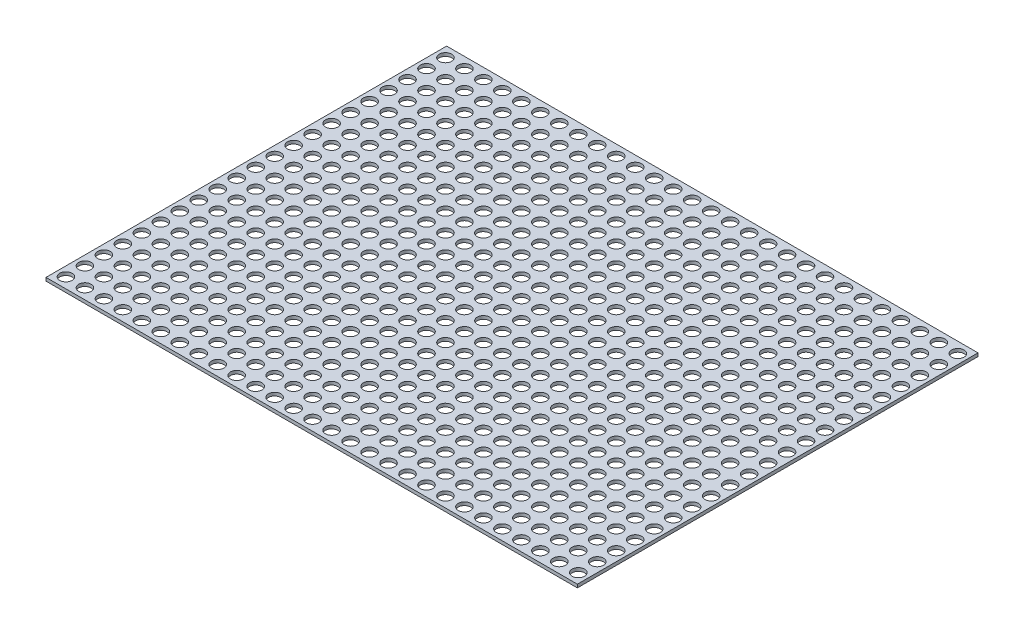
SolidWorks part; units mm, degrees
ref_plane "Front Plane" through (0, 0, 0) normal (0, 0, 1) x (1, 0, 0)
ref_plane "Top Plane" through (0, 0, 0) normal (0, 1, 0) x (1, 0, 0)
ref_plane "Right Plane" through (0, 0, 0) normal (1, 0, 0) x (0, 0, -1)
sketch "Sketch1" plane through (0, 0, 0) normal (0, 1, 0) x (1, 0, 0)
  line L0 (4.5, 4.95) -> (13.5, 4.95) construction
  line L1 (0, 0) -> (252, 0)
  line L2 (0, 0) -> (0, 190)
  line L3 (0, 190) -> (252, 190)
  line L4 (252, 0) -> (252, 190)
  line L5 (4.5, 4.95) -> (4.5, 13.95) construction
  circle A0 centre (4.5, 4.95) radius 2.95
  circle A1 centre (13.5, 4.95) radius 2.95
  circle A2 centre (22.5, 4.95) radius 2.95
  circle A3 centre (31.5, 4.95) radius 2.95
  circle A4 centre (40.5, 4.95) radius 2.95
  circle A5 centre (49.5, 4.95) radius 2.95
  circle A6 centre (58.5, 4.95) radius 2.95
  circle A7 centre (67.5, 4.95) radius 2.95
  circle A8 centre (76.5, 4.95) radius 2.95
  circle A9 centre (85.5, 4.95) radius 2.95
  circle A10 centre (94.5, 4.95) radius 2.95
  circle A11 centre (103.5, 4.95) radius 2.95
  circle A12 centre (112.5, 4.95) radius 2.95
  circle A13 centre (121.5, 4.95) radius 2.95
  circle A14 centre (130.5, 4.95) radius 2.95
  circle A15 centre (139.5, 4.95) radius 2.95
  circle A16 centre (148.5, 4.95) radius 2.95
  circle A17 centre (157.5, 4.95) radius 2.95
  circle A18 centre (166.5, 4.95) radius 2.95
  circle A19 centre (175.5, 4.95) radius 2.95
  circle A20 centre (184.5, 4.95) radius 2.95
  circle A21 centre (193.5, 4.95) radius 2.95
  circle A22 centre (202.5, 4.95) radius 2.95
  circle A23 centre (211.5, 4.95) radius 2.95
  circle A24 centre (220.5, 4.95) radius 2.95
  circle A25 centre (229.5, 4.95) radius 2.95
  circle A26 centre (238.5, 4.95) radius 2.95
  circle A27 centre (247.5, 4.95) radius 2.95
  circle A28 centre (13.5, 13.95) radius 2.95
  circle A29 centre (22.5, 13.95) radius 2.95
  circle A30 centre (31.5, 13.95) radius 2.95
  circle A31 centre (40.5, 13.95) radius 2.95
  circle A32 centre (49.5, 13.95) radius 2.95
  circle A33 centre (58.5, 13.95) radius 2.95
  circle A34 centre (67.5, 13.95) radius 2.95
  circle A35 centre (76.5, 13.95) radius 2.95
  circle A36 centre (85.5, 13.95) radius 2.95
  circle A37 centre (94.5, 13.95) radius 2.95
  circle A38 centre (103.5, 13.95) radius 2.95
  circle A39 centre (112.5, 13.95) radius 2.95
  circle A40 centre (121.5, 13.95) radius 2.95
  circle A41 centre (130.5, 13.95) radius 2.95
  circle A42 centre (139.5, 13.95) radius 2.95
  circle A43 centre (148.5, 13.95) radius 2.95
  circle A44 centre (157.5, 13.95) radius 2.95
  circle A45 centre (166.5, 13.95) radius 2.95
  circle A46 centre (175.5, 13.95) radius 2.95
  circle A47 centre (184.5, 13.95) radius 2.95
  circle A48 centre (193.5, 13.95) radius 2.95
  circle A49 centre (202.5, 13.95) radius 2.95
  circle A50 centre (211.5, 13.95) radius 2.95
  circle A51 centre (220.5, 13.95) radius 2.95
  circle A52 centre (229.5, 13.95) radius 2.95
  circle A53 centre (238.5, 13.95) radius 2.95
  circle A54 centre (247.5, 13.95) radius 2.95
  circle A55 centre (13.5, 22.95) radius 2.95
  circle A56 centre (22.5, 22.95) radius 2.95
  circle A57 centre (31.5, 22.95) radius 2.95
  circle A58 centre (40.5, 22.95) radius 2.95
  circle A59 centre (49.5, 22.95) radius 2.95
  circle A60 centre (58.5, 22.95) radius 2.95
  circle A61 centre (67.5, 22.95) radius 2.95
  circle A62 centre (76.5, 22.95) radius 2.95
  circle A63 centre (85.5, 22.95) radius 2.95
  circle A64 centre (94.5, 22.95) radius 2.95
  circle A65 centre (103.5, 22.95) radius 2.95
  circle A66 centre (112.5, 22.95) radius 2.95
  circle A67 centre (121.5, 22.95) radius 2.95
  circle A68 centre (130.5, 22.95) radius 2.95
  circle A69 centre (139.5, 22.95) radius 2.95
  circle A70 centre (148.5, 22.95) radius 2.95
  circle A71 centre (157.5, 22.95) radius 2.95
  circle A72 centre (166.5, 22.95) radius 2.95
  circle A73 centre (175.5, 22.95) radius 2.95
  circle A74 centre (184.5, 22.95) radius 2.95
  circle A75 centre (193.5, 22.95) radius 2.95
  circle A76 centre (202.5, 22.95) radius 2.95
  circle A77 centre (211.5, 22.95) radius 2.95
  circle A78 centre (220.5, 22.95) radius 2.95
  circle A79 centre (229.5, 22.95) radius 2.95
  circle A80 centre (238.5, 22.95) radius 2.95
  circle A81 centre (247.5, 22.95) radius 2.95
  circle A82 centre (13.5, 31.95) radius 2.95
  circle A83 centre (22.5, 31.95) radius 2.95
  circle A84 centre (31.5, 31.95) radius 2.95
  circle A85 centre (40.5, 31.95) radius 2.95
  circle A86 centre (49.5, 31.95) radius 2.95
  circle A87 centre (58.5, 31.95) radius 2.95
  circle A88 centre (67.5, 31.95) radius 2.95
  circle A89 centre (76.5, 31.95) radius 2.95
  circle A90 centre (85.5, 31.95) radius 2.95
  circle A91 centre (94.5, 31.95) radius 2.95
  circle A92 centre (103.5, 31.95) radius 2.95
  circle A93 centre (112.5, 31.95) radius 2.95
  circle A94 centre (121.5, 31.95) radius 2.95
  circle A95 centre (130.5, 31.95) radius 2.95
  circle A96 centre (139.5, 31.95) radius 2.95
  circle A97 centre (148.5, 31.95) radius 2.95
  circle A98 centre (157.5, 31.95) radius 2.95
  circle A99 centre (166.5, 31.95) radius 2.95
  circle A100 centre (175.5, 31.95) radius 2.95
  circle A101 centre (184.5, 31.95) radius 2.95
  circle A102 centre (193.5, 31.95) radius 2.95
  circle A103 centre (202.5, 31.95) radius 2.95
  circle A104 centre (211.5, 31.95) radius 2.95
  circle A105 centre (220.5, 31.95) radius 2.95
  circle A106 centre (229.5, 31.95) radius 2.95
  circle A107 centre (238.5, 31.95) radius 2.95
  circle A108 centre (247.5, 31.95) radius 2.95
  circle A109 centre (13.5, 40.95) radius 2.95
  circle A110 centre (22.5, 40.95) radius 2.95
  circle A111 centre (31.5, 40.95) radius 2.95
  circle A112 centre (40.5, 40.95) radius 2.95
  circle A113 centre (49.5, 40.95) radius 2.95
  circle A114 centre (58.5, 40.95) radius 2.95
  circle A115 centre (67.5, 40.95) radius 2.95
  circle A116 centre (76.5, 40.95) radius 2.95
  circle A117 centre (85.5, 40.95) radius 2.95
  circle A118 centre (94.5, 40.95) radius 2.95
  circle A119 centre (103.5, 40.95) radius 2.95
  circle A120 centre (112.5, 40.95) radius 2.95
  circle A121 centre (121.5, 40.95) radius 2.95
  circle A122 centre (130.5, 40.95) radius 2.95
  circle A123 centre (139.5, 40.95) radius 2.95
  circle A124 centre (148.5, 40.95) radius 2.95
  circle A125 centre (157.5, 40.95) radius 2.95
  circle A126 centre (166.5, 40.95) radius 2.95
  circle A127 centre (175.5, 40.95) radius 2.95
  circle A128 centre (184.5, 40.95) radius 2.95
  circle A129 centre (193.5, 40.95) radius 2.95
  circle A130 centre (202.5, 40.95) radius 2.95
  circle A131 centre (211.5, 40.95) radius 2.95
  circle A132 centre (220.5, 40.95) radius 2.95
  circle A133 centre (229.5, 40.95) radius 2.95
  circle A134 centre (238.5, 40.95) radius 2.95
  circle A135 centre (247.5, 40.95) radius 2.95
  circle A136 centre (13.5, 49.95) radius 2.95
  circle A137 centre (22.5, 49.95) radius 2.95
  circle A138 centre (31.5, 49.95) radius 2.95
  circle A139 centre (40.5, 49.95) radius 2.95
  circle A140 centre (49.5, 49.95) radius 2.95
  circle A141 centre (58.5, 49.95) radius 2.95
  circle A142 centre (67.5, 49.95) radius 2.95
  circle A143 centre (76.5, 49.95) radius 2.95
  circle A144 centre (85.5, 49.95) radius 2.95
  circle A145 centre (94.5, 49.95) radius 2.95
  circle A146 centre (103.5, 49.95) radius 2.95
  circle A147 centre (112.5, 49.95) radius 2.95
  circle A148 centre (121.5, 49.95) radius 2.95
  circle A149 centre (130.5, 49.95) radius 2.95
  circle A150 centre (139.5, 49.95) radius 2.95
  circle A151 centre (148.5, 49.95) radius 2.95
  circle A152 centre (157.5, 49.95) radius 2.95
  circle A153 centre (166.5, 49.95) radius 2.95
  circle A154 centre (175.5, 49.95) radius 2.95
  circle A155 centre (184.5, 49.95) radius 2.95
  circle A156 centre (193.5, 49.95) radius 2.95
  circle A157 centre (202.5, 49.95) radius 2.95
  circle A158 centre (211.5, 49.95) radius 2.95
  circle A159 centre (220.5, 49.95) radius 2.95
  circle A160 centre (229.5, 49.95) radius 2.95
  circle A161 centre (238.5, 49.95) radius 2.95
  circle A162 centre (247.5, 49.95) radius 2.95
  circle A163 centre (13.5, 58.95) radius 2.95
  circle A164 centre (22.5, 58.95) radius 2.95
  circle A165 centre (31.5, 58.95) radius 2.95
  circle A166 centre (40.5, 58.95) radius 2.95
  circle A167 centre (49.5, 58.95) radius 2.95
  circle A168 centre (58.5, 58.95) radius 2.95
  circle A169 centre (67.5, 58.95) radius 2.95
  circle A170 centre (76.5, 58.95) radius 2.95
  circle A171 centre (85.5, 58.95) radius 2.95
  circle A172 centre (94.5, 58.95) radius 2.95
  circle A173 centre (103.5, 58.95) radius 2.95
  circle A174 centre (112.5, 58.95) radius 2.95
  circle A175 centre (121.5, 58.95) radius 2.95
  circle A176 centre (130.5, 58.95) radius 2.95
  circle A177 centre (139.5, 58.95) radius 2.95
  circle A178 centre (148.5, 58.95) radius 2.95
  circle A179 centre (157.5, 58.95) radius 2.95
  circle A180 centre (166.5, 58.95) radius 2.95
  circle A181 centre (175.5, 58.95) radius 2.95
  circle A182 centre (184.5, 58.95) radius 2.95
  circle A183 centre (193.5, 58.95) radius 2.95
  circle A184 centre (202.5, 58.95) radius 2.95
  circle A185 centre (211.5, 58.95) radius 2.95
  circle A186 centre (220.5, 58.95) radius 2.95
  circle A187 centre (229.5, 58.95) radius 2.95
  circle A188 centre (238.5, 58.95) radius 2.95
  circle A189 centre (247.5, 58.95) radius 2.95
  circle A190 centre (13.5, 67.95) radius 2.95
  circle A191 centre (22.5, 67.95) radius 2.95
  circle A192 centre (31.5, 67.95) radius 2.95
  circle A193 centre (40.5, 67.95) radius 2.95
  circle A194 centre (49.5, 67.95) radius 2.95
  circle A195 centre (58.5, 67.95) radius 2.95
  circle A196 centre (67.5, 67.95) radius 2.95
  circle A197 centre (76.5, 67.95) radius 2.95
  circle A198 centre (85.5, 67.95) radius 2.95
  circle A199 centre (94.5, 67.95) radius 2.95
  circle A200 centre (103.5, 67.95) radius 2.95
  circle A201 centre (112.5, 67.95) radius 2.95
  circle A202 centre (121.5, 67.95) radius 2.95
  circle A203 centre (130.5, 67.95) radius 2.95
  circle A204 centre (139.5, 67.95) radius 2.95
  circle A205 centre (148.5, 67.95) radius 2.95
  circle A206 centre (157.5, 67.95) radius 2.95
  circle A207 centre (166.5, 67.95) radius 2.95
  circle A208 centre (175.5, 67.95) radius 2.95
  circle A209 centre (184.5, 67.95) radius 2.95
  circle A210 centre (193.5, 67.95) radius 2.95
  circle A211 centre (202.5, 67.95) radius 2.95
  circle A212 centre (211.5, 67.95) radius 2.95
  circle A213 centre (220.5, 67.95) radius 2.95
  circle A214 centre (229.5, 67.95) radius 2.95
  circle A215 centre (238.5, 67.95) radius 2.95
  circle A216 centre (247.5, 67.95) radius 2.95
  circle A217 centre (13.5, 76.95) radius 2.95
  circle A218 centre (22.5, 76.95) radius 2.95
  circle A219 centre (31.5, 76.95) radius 2.95
  circle A220 centre (40.5, 76.95) radius 2.95
  circle A221 centre (49.5, 76.95) radius 2.95
  circle A222 centre (58.5, 76.95) radius 2.95
  circle A223 centre (67.5, 76.95) radius 2.95
  circle A224 centre (76.5, 76.95) radius 2.95
  circle A225 centre (85.5, 76.95) radius 2.95
  circle A226 centre (94.5, 76.95) radius 2.95
  circle A227 centre (103.5, 76.95) radius 2.95
  circle A228 centre (112.5, 76.95) radius 2.95
  circle A229 centre (121.5, 76.95) radius 2.95
  circle A230 centre (130.5, 76.95) radius 2.95
  circle A231 centre (139.5, 76.95) radius 2.95
  circle A232 centre (148.5, 76.95) radius 2.95
  circle A233 centre (157.5, 76.95) radius 2.95
  circle A234 centre (166.5, 76.95) radius 2.95
  circle A235 centre (175.5, 76.95) radius 2.95
  circle A236 centre (184.5, 76.95) radius 2.95
  circle A237 centre (193.5, 76.95) radius 2.95
  circle A238 centre (202.5, 76.95) radius 2.95
  circle A239 centre (211.5, 76.95) radius 2.95
  circle A240 centre (220.5, 76.95) radius 2.95
  circle A241 centre (229.5, 76.95) radius 2.95
  circle A242 centre (238.5, 76.95) radius 2.95
  circle A243 centre (247.5, 76.95) radius 2.95
  circle A244 centre (13.5, 85.95) radius 2.95
  circle A245 centre (22.5, 85.95) radius 2.95
  circle A246 centre (31.5, 85.95) radius 2.95
  circle A247 centre (40.5, 85.95) radius 2.95
  circle A248 centre (49.5, 85.95) radius 2.95
  circle A249 centre (58.5, 85.95) radius 2.95
  circle A250 centre (67.5, 85.95) radius 2.95
  circle A251 centre (76.5, 85.95) radius 2.95
  circle A252 centre (85.5, 85.95) radius 2.95
  circle A253 centre (94.5, 85.95) radius 2.95
  circle A254 centre (103.5, 85.95) radius 2.95
  circle A255 centre (112.5, 85.95) radius 2.95
  circle A256 centre (121.5, 85.95) radius 2.95
  circle A257 centre (130.5, 85.95) radius 2.95
  circle A258 centre (139.5, 85.95) radius 2.95
  circle A259 centre (148.5, 85.95) radius 2.95
  circle A260 centre (157.5, 85.95) radius 2.95
  circle A261 centre (166.5, 85.95) radius 2.95
  circle A262 centre (175.5, 85.95) radius 2.95
  circle A263 centre (184.5, 85.95) radius 2.95
  circle A264 centre (193.5, 85.95) radius 2.95
  circle A265 centre (202.5, 85.95) radius 2.95
  circle A266 centre (211.5, 85.95) radius 2.95
  circle A267 centre (220.5, 85.95) radius 2.95
  circle A268 centre (229.5, 85.95) radius 2.95
  circle A269 centre (238.5, 85.95) radius 2.95
  circle A270 centre (247.5, 85.95) radius 2.95
  circle A271 centre (13.5, 94.95) radius 2.95
  circle A272 centre (22.5, 94.95) radius 2.95
  circle A273 centre (31.5, 94.95) radius 2.95
  circle A274 centre (40.5, 94.95) radius 2.95
  circle A275 centre (49.5, 94.95) radius 2.95
  circle A276 centre (58.5, 94.95) radius 2.95
  circle A277 centre (67.5, 94.95) radius 2.95
  circle A278 centre (76.5, 94.95) radius 2.95
  circle A279 centre (85.5, 94.95) radius 2.95
  circle A280 centre (94.5, 94.95) radius 2.95
  circle A281 centre (103.5, 94.95) radius 2.95
  circle A282 centre (112.5, 94.95) radius 2.95
  circle A283 centre (121.5, 94.95) radius 2.95
  circle A284 centre (130.5, 94.95) radius 2.95
  circle A285 centre (139.5, 94.95) radius 2.95
  circle A286 centre (148.5, 94.95) radius 2.95
  circle A287 centre (157.5, 94.95) radius 2.95
  circle A288 centre (166.5, 94.95) radius 2.95
  circle A289 centre (175.5, 94.95) radius 2.95
  circle A290 centre (184.5, 94.95) radius 2.95
  circle A291 centre (193.5, 94.95) radius 2.95
  circle A292 centre (202.5, 94.95) radius 2.95
  circle A293 centre (211.5, 94.95) radius 2.95
  circle A294 centre (220.5, 94.95) radius 2.95
  circle A295 centre (229.5, 94.95) radius 2.95
  circle A296 centre (238.5, 94.95) radius 2.95
  circle A297 centre (247.5, 94.95) radius 2.95
  circle A298 centre (13.5, 103.95) radius 2.95
  circle A299 centre (22.5, 103.95) radius 2.95
  circle A300 centre (31.5, 103.95) radius 2.95
  circle A301 centre (40.5, 103.95) radius 2.95
  circle A302 centre (49.5, 103.95) radius 2.95
  circle A303 centre (58.5, 103.95) radius 2.95
  circle A304 centre (67.5, 103.95) radius 2.95
  circle A305 centre (76.5, 103.95) radius 2.95
  circle A306 centre (85.5, 103.95) radius 2.95
  circle A307 centre (94.5, 103.95) radius 2.95
  circle A308 centre (103.5, 103.95) radius 2.95
  circle A309 centre (112.5, 103.95) radius 2.95
  circle A310 centre (121.5, 103.95) radius 2.95
  circle A311 centre (130.5, 103.95) radius 2.95
  circle A312 centre (139.5, 103.95) radius 2.95
  circle A313 centre (148.5, 103.95) radius 2.95
  circle A314 centre (157.5, 103.95) radius 2.95
  circle A315 centre (166.5, 103.95) radius 2.95
  circle A316 centre (175.5, 103.95) radius 2.95
  circle A317 centre (184.5, 103.95) radius 2.95
  circle A318 centre (193.5, 103.95) radius 2.95
  circle A319 centre (202.5, 103.95) radius 2.95
  circle A320 centre (211.5, 103.95) radius 2.95
  circle A321 centre (220.5, 103.95) radius 2.95
  circle A322 centre (229.5, 103.95) radius 2.95
  circle A323 centre (238.5, 103.95) radius 2.95
  circle A324 centre (247.5, 103.95) radius 2.95
  circle A325 centre (13.5, 112.95) radius 2.95
  circle A326 centre (22.5, 112.95) radius 2.95
  circle A327 centre (31.5, 112.95) radius 2.95
  circle A328 centre (40.5, 112.95) radius 2.95
  circle A329 centre (49.5, 112.95) radius 2.95
  circle A330 centre (58.5, 112.95) radius 2.95
  circle A331 centre (67.5, 112.95) radius 2.95
  circle A332 centre (76.5, 112.95) radius 2.95
  circle A333 centre (85.5, 112.95) radius 2.95
  circle A334 centre (94.5, 112.95) radius 2.95
  circle A335 centre (103.5, 112.95) radius 2.95
  circle A336 centre (112.5, 112.95) radius 2.95
  circle A337 centre (121.5, 112.95) radius 2.95
  circle A338 centre (130.5, 112.95) radius 2.95
  circle A339 centre (139.5, 112.95) radius 2.95
  circle A340 centre (148.5, 112.95) radius 2.95
  circle A341 centre (157.5, 112.95) radius 2.95
  circle A342 centre (166.5, 112.95) radius 2.95
  circle A343 centre (175.5, 112.95) radius 2.95
  circle A344 centre (184.5, 112.95) radius 2.95
  circle A345 centre (193.5, 112.95) radius 2.95
  circle A346 centre (202.5, 112.95) radius 2.95
  circle A347 centre (211.5, 112.95) radius 2.95
  circle A348 centre (220.5, 112.95) radius 2.95
  circle A349 centre (229.5, 112.95) radius 2.95
  circle A350 centre (238.5, 112.95) radius 2.95
  circle A351 centre (247.5, 112.95) radius 2.95
  circle A352 centre (13.5, 121.95) radius 2.95
  circle A353 centre (22.5, 121.95) radius 2.95
  circle A354 centre (31.5, 121.95) radius 2.95
  circle A355 centre (40.5, 121.95) radius 2.95
  circle A356 centre (49.5, 121.95) radius 2.95
  circle A357 centre (58.5, 121.95) radius 2.95
  circle A358 centre (67.5, 121.95) radius 2.95
  circle A359 centre (76.5, 121.95) radius 2.95
  circle A360 centre (85.5, 121.95) radius 2.95
  circle A361 centre (94.5, 121.95) radius 2.95
  circle A362 centre (103.5, 121.95) radius 2.95
  circle A363 centre (112.5, 121.95) radius 2.95
  circle A364 centre (121.5, 121.95) radius 2.95
  circle A365 centre (130.5, 121.95) radius 2.95
  circle A366 centre (139.5, 121.95) radius 2.95
  circle A367 centre (148.5, 121.95) radius 2.95
  circle A368 centre (157.5, 121.95) radius 2.95
  circle A369 centre (166.5, 121.95) radius 2.95
  circle A370 centre (175.5, 121.95) radius 2.95
  circle A371 centre (184.5, 121.95) radius 2.95
  circle A372 centre (193.5, 121.95) radius 2.95
  circle A373 centre (202.5, 121.95) radius 2.95
  circle A374 centre (211.5, 121.95) radius 2.95
  circle A375 centre (220.5, 121.95) radius 2.95
  circle A376 centre (229.5, 121.95) radius 2.95
  circle A377 centre (238.5, 121.95) radius 2.95
  circle A378 centre (247.5, 121.95) radius 2.95
  circle A379 centre (13.5, 130.95) radius 2.95
  circle A380 centre (22.5, 130.95) radius 2.95
  circle A381 centre (31.5, 130.95) radius 2.95
  circle A382 centre (40.5, 130.95) radius 2.95
  circle A383 centre (49.5, 130.95) radius 2.95
  circle A384 centre (58.5, 130.95) radius 2.95
  circle A385 centre (67.5, 130.95) radius 2.95
  circle A386 centre (76.5, 130.95) radius 2.95
  circle A387 centre (85.5, 130.95) radius 2.95
  circle A388 centre (94.5, 130.95) radius 2.95
  circle A389 centre (103.5, 130.95) radius 2.95
  circle A390 centre (112.5, 130.95) radius 2.95
  circle A391 centre (121.5, 130.95) radius 2.95
  circle A392 centre (130.5, 130.95) radius 2.95
  circle A393 centre (139.5, 130.95) radius 2.95
  circle A394 centre (148.5, 130.95) radius 2.95
  circle A395 centre (157.5, 130.95) radius 2.95
  circle A396 centre (166.5, 130.95) radius 2.95
  circle A397 centre (175.5, 130.95) radius 2.95
  circle A398 centre (184.5, 130.95) radius 2.95
  circle A399 centre (193.5, 130.95) radius 2.95
  circle A400 centre (202.5, 130.95) radius 2.95
  circle A401 centre (211.5, 130.95) radius 2.95
  circle A402 centre (220.5, 130.95) radius 2.95
  circle A403 centre (229.5, 130.95) radius 2.95
  circle A404 centre (238.5, 130.95) radius 2.95
  circle A405 centre (247.5, 130.95) radius 2.95
  circle A406 centre (13.5, 139.95) radius 2.95
  circle A407 centre (22.5, 139.95) radius 2.95
  circle A408 centre (31.5, 139.95) radius 2.95
  circle A409 centre (40.5, 139.95) radius 2.95
  circle A410 centre (49.5, 139.95) radius 2.95
  circle A411 centre (58.5, 139.95) radius 2.95
  circle A412 centre (67.5, 139.95) radius 2.95
  circle A413 centre (76.5, 139.95) radius 2.95
  circle A414 centre (85.5, 139.95) radius 2.95
  circle A415 centre (94.5, 139.95) radius 2.95
  circle A416 centre (103.5, 139.95) radius 2.95
  circle A417 centre (112.5, 139.95) radius 2.95
  circle A418 centre (121.5, 139.95) radius 2.95
  circle A419 centre (130.5, 139.95) radius 2.95
  circle A420 centre (139.5, 139.95) radius 2.95
  circle A421 centre (148.5, 139.95) radius 2.95
  circle A422 centre (157.5, 139.95) radius 2.95
  circle A423 centre (166.5, 139.95) radius 2.95
  circle A424 centre (175.5, 139.95) radius 2.95
  circle A425 centre (184.5, 139.95) radius 2.95
  circle A426 centre (193.5, 139.95) radius 2.95
  circle A427 centre (202.5, 139.95) radius 2.95
  circle A428 centre (211.5, 139.95) radius 2.95
  circle A429 centre (220.5, 139.95) radius 2.95
  circle A430 centre (229.5, 139.95) radius 2.95
  circle A431 centre (238.5, 139.95) radius 2.95
  circle A432 centre (247.5, 139.95) radius 2.95
  circle A433 centre (13.5, 148.95) radius 2.95
  circle A434 centre (22.5, 148.95) radius 2.95
  circle A435 centre (31.5, 148.95) radius 2.95
  circle A436 centre (40.5, 148.95) radius 2.95
  circle A437 centre (49.5, 148.95) radius 2.95
  circle A438 centre (58.5, 148.95) radius 2.95
  circle A439 centre (67.5, 148.95) radius 2.95
  circle A440 centre (76.5, 148.95) radius 2.95
  circle A441 centre (85.5, 148.95) radius 2.95
  circle A442 centre (94.5, 148.95) radius 2.95
  circle A443 centre (103.5, 148.95) radius 2.95
  circle A444 centre (112.5, 148.95) radius 2.95
  circle A445 centre (121.5, 148.95) radius 2.95
  circle A446 centre (130.5, 148.95) radius 2.95
  circle A447 centre (139.5, 148.95) radius 2.95
  circle A448 centre (148.5, 148.95) radius 2.95
  circle A449 centre (157.5, 148.95) radius 2.95
  circle A450 centre (166.5, 148.95) radius 2.95
  circle A451 centre (175.5, 148.95) radius 2.95
  circle A452 centre (184.5, 148.95) radius 2.95
  circle A453 centre (193.5, 148.95) radius 2.95
  circle A454 centre (202.5, 148.95) radius 2.95
  circle A455 centre (211.5, 148.95) radius 2.95
  circle A456 centre (220.5, 148.95) radius 2.95
  circle A457 centre (229.5, 148.95) radius 2.95
  circle A458 centre (238.5, 148.95) radius 2.95
  circle A459 centre (247.5, 148.95) radius 2.95
  circle A460 centre (13.5, 157.95) radius 2.95
  circle A461 centre (22.5, 157.95) radius 2.95
  circle A462 centre (31.5, 157.95) radius 2.95
  circle A463 centre (40.5, 157.95) radius 2.95
  circle A464 centre (49.5, 157.95) radius 2.95
  circle A465 centre (58.5, 157.95) radius 2.95
  circle A466 centre (67.5, 157.95) radius 2.95
  circle A467 centre (76.5, 157.95) radius 2.95
  circle A468 centre (85.5, 157.95) radius 2.95
  circle A469 centre (94.5, 157.95) radius 2.95
  circle A470 centre (103.5, 157.95) radius 2.95
  circle A471 centre (112.5, 157.95) radius 2.95
  circle A472 centre (121.5, 157.95) radius 2.95
  circle A473 centre (130.5, 157.95) radius 2.95
  circle A474 centre (139.5, 157.95) radius 2.95
  circle A475 centre (148.5, 157.95) radius 2.95
  circle A476 centre (157.5, 157.95) radius 2.95
  circle A477 centre (166.5, 157.95) radius 2.95
  circle A478 centre (175.5, 157.95) radius 2.95
  circle A479 centre (184.5, 157.95) radius 2.95
  circle A480 centre (193.5, 157.95) radius 2.95
  circle A481 centre (202.5, 157.95) radius 2.95
  circle A482 centre (211.5, 157.95) radius 2.95
  circle A483 centre (220.5, 157.95) radius 2.95
  circle A484 centre (229.5, 157.95) radius 2.95
  circle A485 centre (238.5, 157.95) radius 2.95
  circle A486 centre (247.5, 157.95) radius 2.95
  circle A487 centre (13.5, 166.95) radius 2.95
  circle A488 centre (22.5, 166.95) radius 2.95
  circle A489 centre (31.5, 166.95) radius 2.95
  circle A490 centre (40.5, 166.95) radius 2.95
  circle A491 centre (49.5, 166.95) radius 2.95
  circle A492 centre (58.5, 166.95) radius 2.95
  circle A493 centre (67.5, 166.95) radius 2.95
  circle A494 centre (76.5, 166.95) radius 2.95
  circle A495 centre (85.5, 166.95) radius 2.95
  circle A496 centre (94.5, 166.95) radius 2.95
  circle A497 centre (103.5, 166.95) radius 2.95
  circle A498 centre (112.5, 166.95) radius 2.95
  circle A499 centre (121.5, 166.95) radius 2.95
  circle A500 centre (130.5, 166.95) radius 2.95
  circle A501 centre (139.5, 166.95) radius 2.95
  circle A502 centre (148.5, 166.95) radius 2.95
  circle A503 centre (157.5, 166.95) radius 2.95
  circle A504 centre (166.5, 166.95) radius 2.95
  circle A505 centre (175.5, 166.95) radius 2.95
  circle A506 centre (184.5, 166.95) radius 2.95
  circle A507 centre (193.5, 166.95) radius 2.95
  circle A508 centre (202.5, 166.95) radius 2.95
  circle A509 centre (211.5, 166.95) radius 2.95
  circle A510 centre (220.5, 166.95) radius 2.95
  circle A511 centre (229.5, 166.95) radius 2.95
  circle A512 centre (238.5, 166.95) radius 2.95
  circle A513 centre (247.5, 166.95) radius 2.95
  circle A514 centre (13.5, 175.95) radius 2.95
  circle A515 centre (22.5, 175.95) radius 2.95
  circle A516 centre (31.5, 175.95) radius 2.95
  circle A517 centre (40.5, 175.95) radius 2.95
  circle A518 centre (49.5, 175.95) radius 2.95
  circle A519 centre (58.5, 175.95) radius 2.95
  circle A520 centre (67.5, 175.95) radius 2.95
  circle A521 centre (76.5, 175.95) radius 2.95
  circle A522 centre (85.5, 175.95) radius 2.95
  circle A523 centre (94.5, 175.95) radius 2.95
  circle A524 centre (103.5, 175.95) radius 2.95
  circle A525 centre (112.5, 175.95) radius 2.95
  circle A526 centre (121.5, 175.95) radius 2.95
  circle A527 centre (130.5, 175.95) radius 2.95
  circle A528 centre (139.5, 175.95) radius 2.95
  circle A529 centre (148.5, 175.95) radius 2.95
  circle A530 centre (157.5, 175.95) radius 2.95
  circle A531 centre (166.5, 175.95) radius 2.95
  circle A532 centre (175.5, 175.95) radius 2.95
  circle A533 centre (184.5, 175.95) radius 2.95
  circle A534 centre (193.5, 175.95) radius 2.95
  circle A535 centre (202.5, 175.95) radius 2.95
  circle A536 centre (211.5, 175.95) radius 2.95
  circle A537 centre (220.5, 175.95) radius 2.95
  circle A538 centre (229.5, 175.95) radius 2.95
  circle A539 centre (238.5, 175.95) radius 2.95
  circle A540 centre (247.5, 175.95) radius 2.95
  circle A541 centre (13.5, 184.95) radius 2.95
  circle A542 centre (22.5, 184.95) radius 2.95
  circle A543 centre (31.5, 184.95) radius 2.95
  circle A544 centre (40.5, 184.95) radius 2.95
  circle A545 centre (49.5, 184.95) radius 2.95
  circle A546 centre (58.5, 184.95) radius 2.95
  circle A547 centre (67.5, 184.95) radius 2.95
  circle A548 centre (76.5, 184.95) radius 2.95
  circle A549 centre (85.5, 184.95) radius 2.95
  circle A550 centre (94.5, 184.95) radius 2.95
  circle A551 centre (103.5, 184.95) radius 2.95
  circle A552 centre (112.5, 184.95) radius 2.95
  circle A553 centre (121.5, 184.95) radius 2.95
  circle A554 centre (130.5, 184.95) radius 2.95
  circle A555 centre (139.5, 184.95) radius 2.95
  circle A556 centre (148.5, 184.95) radius 2.95
  circle A557 centre (157.5, 184.95) radius 2.95
  circle A558 centre (166.5, 184.95) radius 2.95
  circle A559 centre (175.5, 184.95) radius 2.95
  circle A560 centre (184.5, 184.95) radius 2.95
  circle A561 centre (193.5, 184.95) radius 2.95
  circle A562 centre (202.5, 184.95) radius 2.95
  circle A563 centre (211.5, 184.95) radius 2.95
  circle A564 centre (220.5, 184.95) radius 2.95
  circle A565 centre (229.5, 184.95) radius 2.95
  circle A566 centre (238.5, 184.95) radius 2.95
  circle A567 centre (247.5, 184.95) radius 2.95
  circle A568 centre (4.5, 13.95) radius 2.95
  circle A569 centre (4.5, 22.95) radius 2.95
  circle A570 centre (4.5, 31.95) radius 2.95
  circle A571 centre (4.5, 40.95) radius 2.95
  circle A572 centre (4.5, 49.95) radius 2.95
  circle A573 centre (4.5, 58.95) radius 2.95
  circle A574 centre (4.5, 67.95) radius 2.95
  circle A575 centre (4.5, 76.95) radius 2.95
  circle A576 centre (4.5, 85.95) radius 2.95
  circle A577 centre (4.5, 94.95) radius 2.95
  circle A578 centre (4.5, 103.95) radius 2.95
  circle A579 centre (4.5, 112.95) radius 2.95
  circle A580 centre (4.5, 121.95) radius 2.95
  circle A581 centre (4.5, 130.95) radius 2.95
  circle A582 centre (4.5, 139.95) radius 2.95
  circle A583 centre (4.5, 148.95) radius 2.95
  circle A584 centre (4.5, 157.95) radius 2.95
  circle A585 centre (4.5, 166.95) radius 2.95
  circle A586 centre (4.5, 175.95) radius 2.95
  circle A587 centre (4.5, 184.95) radius 2.95
  dimension "D3" = 5.9
  dimension "D1" = 252
  dimension "D2" = 190
  dimension "D4" = 4.95
  dimension "D5" = 4.5
  dimension "D8" = 9
  dimension "D9" = 9
  dimension "D6" = 28
  dimension "D7" = 21
extrude "Boss-Extrude1" add sketch "Sketch1" along normal blind 1.55 contours L1 L4 L3 L2 A587 A586 A585 A584 A583 A582 A581 A580 A579 A578 A577 A576 A575 A574 A573 A572 A571 A570 A569 A568 A567 A566 A565 region at (126, 0, -95.0253)
equation "\"Length\" = 283"
equation "\"Width\" = 225"
equation "\"WallThickness\" = 12.5"
equation "\"UpperWaterJacketThickness\" = 28"
equation "\"SpacerHeight\" = 80.2"
equation "\"PlateLength\"=252"
equation "\"D1@Sketch1\"=\"PlateLength\""
equation "\"PlateWidth\"=190"
equation "\"D2@Sketch1\"=\"PlateWidth\""
equation "\"PlateHoleDiameter\"=5.9"
equation "\"D3@Sketch1\"=\"PlateHoleDiameter\""
equation "\"PlateHoleBottom\"= 2"
equation "\"D4@Sketch1\"=\"PlateHoleBottom\"+\"PlateHoleDiameter\"/2"
equation "\"PlateHoleSide\"= 1.55"
equation "\"D5@Sketch1\"=\"PlateHoleSide\"+\"PlateHoleDiameter\"/2"
equation "\"PlateHoleSpacing\"= 3.1"
equation "\"D8@Sketch1\"=\"PlateHoleSpacing\"+\"PlateHoleDiameter\""
equation "\"D9@Sketch1\"=\"PlateHoleSpacing\"+\"PlateHoleDiameter\""
equation "\"PlateThickness\"=1.55"
equation "\"D1@Boss-Extrude1\"=\"PlateThickness\""
